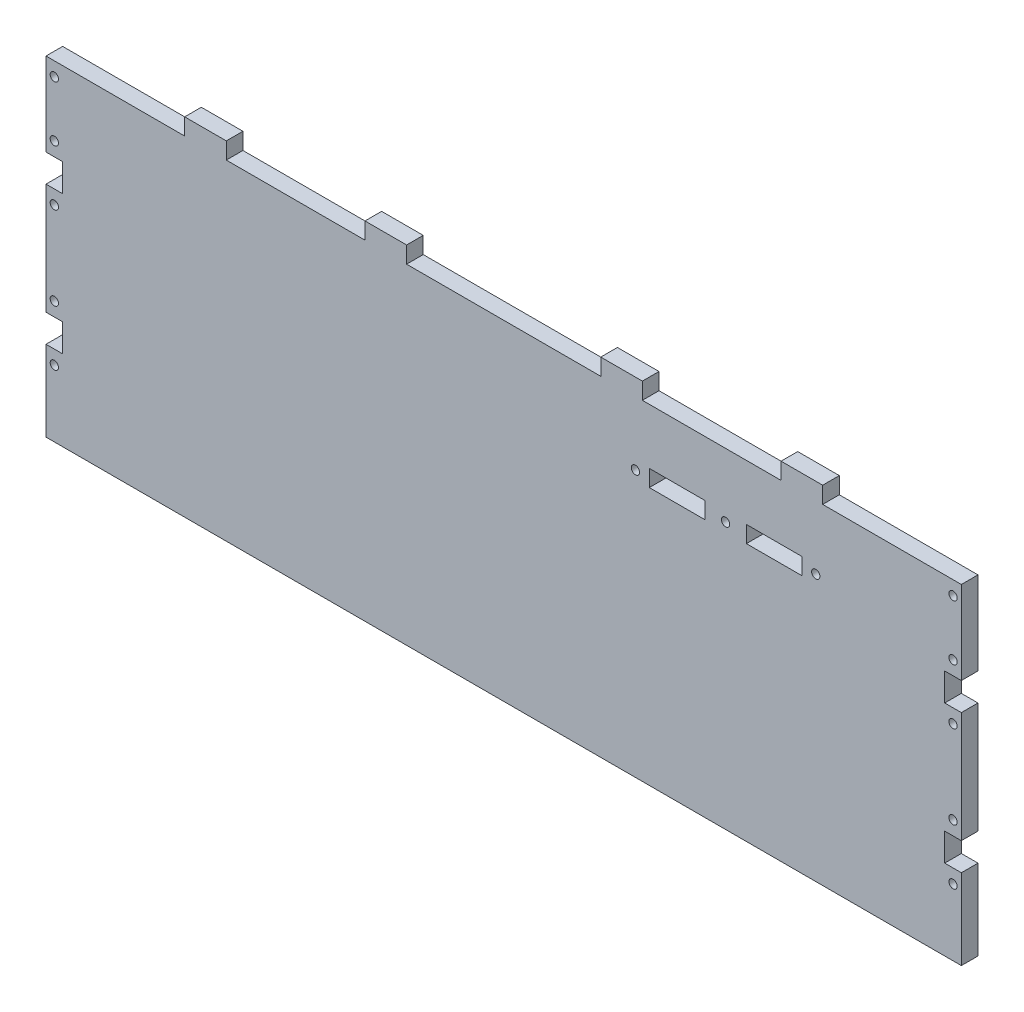
SolidWorks part; units mm, degrees
ref_plane "Plan de face" through (0, 0, 0) normal (0, 0, 1) x (1, 0, 0)
ref_plane "Plan de dessus" through (0, 0, 0) normal (0, 1, 0) x (1, 0, 0)
ref_plane "Plan de droite" through (0, 0, 0) normal (1, 0, 0) x (0, 0, -1)
sketch "Esquisse1" plane through (0, 0, 0) normal (0, 0, 1) x (1, 0, 0)
  line L0 (97.3951, 0) -> (-118.5049, 0) construction
  line L1 (-165, 119) -> (165, 119)
  line L2 (-165, 119) -> (-165, -119)
  line L3 (-165, -119) -> (165, -119)
  line L4 (165, 119) -> (165, -119)
  line L5 (0, 79.3588) -> (0, -79.3588) construction
  line L6 (-92.5, -55) -> (-77.5, -55)
  line L7 (-92.5, -55) -> (-92.5, -61)
  line L8 (-92.5, -61) -> (-77.5, -61)
  line L9 (-77.5, -55) -> (-77.5, -61)
  line L10 (-7.5, -55) -> (7.5, -55)
  line L11 (-7.5, -55) -> (-7.5, -61)
  line L12 (-7.5, -61) -> (7.5, -61)
  line L13 (7.5, -55) -> (7.5, -61)
  line L14 (77.5, -55) -> (92.5, -55)
  line L15 (77.5, -55) -> (77.5, -61)
  line L16 (77.5, -61) -> (92.5, -61)
  line L17 (92.5, -55) -> (92.5, -61)
  line L19 (52.5, 99) -> (72.5, 99)
  line L20 (52.5, 99) -> (52.5, 93)
  line L21 (52.5, 93) -> (72.5, 93)
  line L22 (72.5, 99) -> (72.5, 93)
  line L23 (87.5, 99) -> (107.5, 99)
  line L24 (87.5, 99) -> (87.5, 93)
  line L25 (87.5, 93) -> (107.5, 93)
  line L26 (107.5, 99) -> (107.5, 93)
  dimension "D1" = 238
  dimension "D2" = 330
  dimension "D3" = 165
  dimension "D4" = 119
  dimension "D5" = 15
  dimension "D6" = 6
  dimension "D7" = 6
  dimension "D8" = 15
  dimension "D9" = 6
  dimension "D10" = 15
  dimension "D11" = 70
  dimension "D12" = 70
  dimension "D13" = 58
  dimension "D14" = 72.5
  dimension "D15" = 6
  dimension "D16" = 20
  dimension "D17" = 20
  dimension "D18" = 6
  dimension "D19" = 15
  dimension "D20" = 57.5
  dimension "D21" = 20
  dimension "D22" = 20
extrude "Boss.-Extru.1" add sketch "Esquisse1" along normal blind 6
sketch "Esquisse2" plane through (0, 0, 6) normal (0, 0, 1) x (1, 0, 0)
  line L0 (243.146, 0) -> (-260.0003, 0) construction
  line L1 (0, 180.4713) -> (0, -129.6072) construction
  line L2 (165, 119) -> (-165, 119) construction
  line L3 (-115, 119) -> (-100, 119)
  line L4 (-115, 119) -> (-115, 125)
  line L5 (-115, 125) -> (-100, 125)
  line L6 (-100, 119) -> (-100, 125)
  line L7 (-165, 119) -> (-165, -119) construction
  line L8 (-50, 119) -> (-35, 119)
  line L9 (-50, 119) -> (-50, 125)
  line L10 (-50, 125) -> (-35, 125)
  line L11 (-35, 119) -> (-35, 125)
  line L12 (35, 119) -> (35, 125)
  line L13 (50, 125) -> (35, 125)
  line L14 (50, 119) -> (50, 125)
  line L15 (50, 119) -> (35, 119)
  line L16 (100, 119) -> (100, 125)
  line L17 (115, 125) -> (100, 125)
  line L18 (115, 119) -> (115, 125)
  line L19 (115, 119) -> (100, 119)
  line L20 (-115, 119) -> (-100, 119)
  line L21 (-115, 119) -> (-115, 125)
  line L22 (-115, 125) -> (-100, 125)
  line L23 (-100, 119) -> (-100, 125)
  line L24 (-50, 119) -> (-35, 119)
  line L25 (-50, 119) -> (-50, 125)
  line L26 (-50, 125) -> (-35, 125)
  line L27 (-35, 119) -> (-35, 125)
  line L28 (35, 119) -> (35, 125)
  line L29 (50, 125) -> (35, 125)
  line L30 (50, 119) -> (50, 125)
  line L31 (50, 119) -> (35, 119)
  line L32 (100, 119) -> (100, 125)
  line L33 (115, 125) -> (100, 125)
  line L34 (115, 119) -> (115, 125)
  line L35 (115, 119) -> (100, 119)
  line L36 (115, -119) -> (100, -119)
  line L37 (115, -119) -> (115, -125)
  line L38 (115, -125) -> (100, -125)
  line L39 (100, -119) -> (100, -125)
  line L40 (50, -119) -> (35, -119)
  line L41 (50, -119) -> (50, -125)
  line L42 (50, -125) -> (35, -125)
  line L43 (35, -119) -> (35, -125)
  line L44 (-35, -119) -> (-35, -125)
  line L45 (-50, -125) -> (-35, -125)
  line L46 (-50, -119) -> (-50, -125)
  line L47 (-50, -119) -> (-35, -119)
  line L48 (-100, -119) -> (-100, -125)
  line L49 (-115, -125) -> (-100, -125)
  line L50 (-115, -119) -> (-115, -125)
  line L51 (-115, -119) -> (-100, -119)
  line L52 (115, -119) -> (100, -119)
  line L53 (115, -119) -> (115, -125)
  line L54 (115, -125) -> (100, -125)
  line L55 (100, -119) -> (100, -125)
  line L56 (50, -119) -> (35, -119)
  line L57 (50, -119) -> (50, -125)
  line L58 (50, -125) -> (35, -125)
  line L59 (35, -119) -> (35, -125)
  line L60 (-35, -119) -> (-35, -125)
  line L61 (-50, -125) -> (-35, -125)
  line L62 (-50, -119) -> (-50, -125)
  line L63 (-50, -119) -> (-35, -119)
  line L64 (-100, -119) -> (-100, -125)
  line L65 (-115, -125) -> (-100, -125)
  line L66 (-115, -119) -> (-115, -125)
  line L67 (-115, -119) -> (-100, -119)
  line M9 (-165, -119) -> (165, -119)
  line M11 (165, 119) -> (-165, 119)
  dimension "D1" = 6
  dimension "D2" = 6
  dimension "D3" = 15
  dimension "D4" = 15
  dimension "D5" = 50
  dimension "D6" = 50
extrude "Boss.-Extru.2" add sketch "Esquisse2" against normal blind 6 contours L6 L5 L4 M11 | L11 L10 L9 M11 | L14 L13 L12 M11 | L18 L17 L16 M11 | L39 L38 L37 M9 | L43 L42 L41 M9 | L46 L45 L44 M9 | L50 L49 L48 M9 region at (-107.5, 122, 6) region at (107.5, 122, 6) region at (42.5, 122, 6) region at (-42.5, 122, 6) region at (107.5, -122, 6) region at (-107.5, -122, 6) region at (-42.5, -122, 6) region at (42.5, -122, 6)
sketch "Esquisse3" plane through (0, 0, 6) normal (0, 0, 1) x (1, 0, 0)
  line L0 (-165, 119) -> (-165, -119) construction
  line L1 (-165, 79) -> (-159, 79)
  line L2 (-165, 79) -> (-165, 89)
  line L3 (-165, 89) -> (-159, 89)
  line L4 (-159, 79) -> (-159, 89)
  line L5 (234.1368, 0) -> (-337.9213, 0) construction
  line L6 (-165, 39) -> (-159, 39)
  line L7 (-165, 39) -> (-165, 29)
  line L8 (-165, 29) -> (-159, 29)
  line L9 (-159, 39) -> (-159, 29)
  line L10 (0, 279.7488) -> (0, -188.1201) construction
  line L11 (-115, 119) -> (-165, 119) construction
  line L12 (-159, -39) -> (-159, -29)
  line L13 (-165, -29) -> (-159, -29)
  line L14 (-165, -39) -> (-165, -29)
  line L15 (-165, -39) -> (-159, -39)
  line L16 (-159, -79) -> (-159, -89)
  line L17 (-165, -89) -> (-159, -89)
  line L18 (-165, -79) -> (-165, -89)
  line L19 (-165, -79) -> (-159, -79)
  line L20 (165, -79) -> (159, -79)
  line L21 (165, -79) -> (165, -89)
  line L22 (165, -89) -> (159, -89)
  line L23 (159, -79) -> (159, -89)
  line L24 (165, -39) -> (159, -39)
  line L25 (165, -39) -> (165, -29)
  line L26 (165, -29) -> (159, -29)
  line L27 (159, -39) -> (159, -29)
  line L28 (159, 39) -> (159, 29)
  line L29 (165, 29) -> (159, 29)
  line L30 (165, 39) -> (165, 29)
  line L31 (165, 39) -> (159, 39)
  line L32 (159, 79) -> (159, 89)
  line L33 (165, 89) -> (159, 89)
  line L34 (165, 79) -> (165, 89)
  line L35 (165, 79) -> (159, 79)
  line L36 (153, -119) -> (153, -109)
  line L37 (-165, -119) -> (-153, -119)
  line L38 (-165, -119) -> (-165, -109)
  line L39 (-165, -109) -> (-153, -109)
  line L40 (-153, -119) -> (-153, -109)
  line L41 (165, -109) -> (153, -109)
  line L42 (165, -119) -> (165, -109)
  line L43 (165, -119) -> (153, -119)
  dimension "D1" = 40
  dimension "D2" = 6
  dimension "D3" = 6
  dimension "D4" = 10
  dimension "D5" = 10
  dimension "D6" = 30
  dimension "D7" = 12
  dimension "D8" = 10
extrude "Enlèv. mat.-Extru.1" cut sketch "Esquisse3" against normal blind 6
sketch "Esquisse4" plane through (0, 0, 6) normal (0, 0, 1) x (1, 0, 0)
  line L0 (-162, 121.7279) -> (-162, -131.0602) construction
  line L1 (0, 158.5579) -> (0, -182.4489) construction
  line L2 (-115, 119) -> (-165, 119) construction
  line L3 (-106.4439, -58) -> (117.3944, -58) construction
  line L4 (-159, 89) -> (-165, 89) construction
  line L5 (-165, 119) -> (-165, 89) construction
  line L6 (-165, 79) -> (-159, 79) construction
  line L7 (-159, 39) -> (-165, 39) construction
  line L8 (-165, 29) -> (-159, 29) construction
  line L9 (-159, -29) -> (-165, -29) construction
  line L10 (-92.5, -55) -> (-92.5, -61) construction
  line L11 (-77.5, -61) -> (-77.5, -55) construction
  line L12 (-165, -39) -> (-159, -39) construction
  line L13 (-159, -79) -> (-165, -79) construction
  line L14 (-165, -89) -> (-159, -89) construction
  line L15 (-7.5, -55) -> (-7.5, -61) construction
  line L16 (162, 121.7279) -> (162, -131.0602) construction
  line L17 (116.5184, 96) -> (43.4816, 96) construction
  line L20 (52.5, 99) -> (52.5, 93) construction
  line L21 (72.5, 93) -> (72.5, 99) construction
  line L22 (107.5, 93) -> (107.5, 99) construction
  line L23 (52.5, 93) -> (72.5, 93) construction
  circle A0 centre (-162, 114) radius 1.5
  circle A1 centre (-162, 94) radius 1.5
  circle A2 centre (-162, 74) radius 1.5
  circle A3 centre (-162, 44) radius 1.5
  circle A4 centre (-162, 24) radius 1.5
  circle A5 centre (47.5, 96) radius 1.5
  circle A6 centre (-162, -24) radius 1.5
  circle A7 centre (-162, -44) radius 1.5
  circle A8 centre (-162, -74) radius 1.5
  circle A9 centre (-162, -94) radius 1.5
  circle A10 centre (-97.5, -58) radius 1.5
  circle A11 centre (-72.5, -58) radius 1.5
  circle A12 centre (162, -94) radius 1.5
  circle A13 centre (162, -74) radius 1.5
  circle A14 centre (162, -44) radius 1.5
  circle A15 centre (162, -24) radius 1.5
  circle A16 centre (80, 96) radius 1.5
  circle A17 centre (162, 24) radius 1.5
  circle A18 centre (162, 44) radius 1.5
  circle A19 centre (162, 74) radius 1.5
  circle A20 centre (162, 94) radius 1.5
  circle A21 centre (162, 114) radius 1.5
  circle A22 centre (-12.5, -58) radius 1.5
  circle A23 centre (12.5, -58) radius 1.5
  circle A24 centre (72.5, -58) radius 1.5
  circle A25 centre (97.5, -58) radius 1.5
  circle A26 centre (112.5, 96) radius 1.5
  dimension "D1" = 3
  dimension "D2" = 3
  dimension "D3" = 3
  dimension "D4" = 3
  dimension "D5" = 3
  dimension "D6" = 3
  dimension "D7" = 3
  dimension "D8" = 3
  dimension "D9" = 3
  dimension "D10" = 3
  dimension "D11" = 3
  dimension "D12" = 5
  dimension "D13" = 5
  dimension "D15" = 5
  dimension "D16" = 5
  dimension "D17" = 5
  dimension "D19" = 3
  dimension "D20" = 5
  dimension "D21" = 5
  dimension "D23" = 3
  dimension "D24" = 3
  dimension "D25" = 5
  dimension "D26" = 5
  dimension "D27" = 5
  dimension "D28" = 3
  dimension "D29" = 5
  dimension "D30" = 7.5
  dimension "D31" = 5
  dimension "D14" = 3
  dimension "D18" = 5
  dimension "D22" = 5
  dimension "D32" = 3
extrude "Enlèv. mat.-Extru.2" cut sketch "Esquisse4" against normal blind 6
sketch "Esquisse5" plane through (0, 0, 6) normal (0, 0, 1) x (1, 0, 0)
  line L1 (-200.0968, 0) -> (223.5072, 0)
  line L2 (-200.0968, 0) -> (-200.0968, -150.3561)
  line L3 (-200.0968, -150.3561) -> (223.5072, -150.3561)
  line L4 (223.5072, 0) -> (223.5072, -150.3561)
extrude "Enlèv. mat.-Extru.3" cut sketch "Esquisse5" against normal blind 6
equation "\"D3@Esquisse1\"=\"D2@Esquisse1\"/2"
equation "\"D4@Esquisse1\"=\"D1@Esquisse1\"/2"
